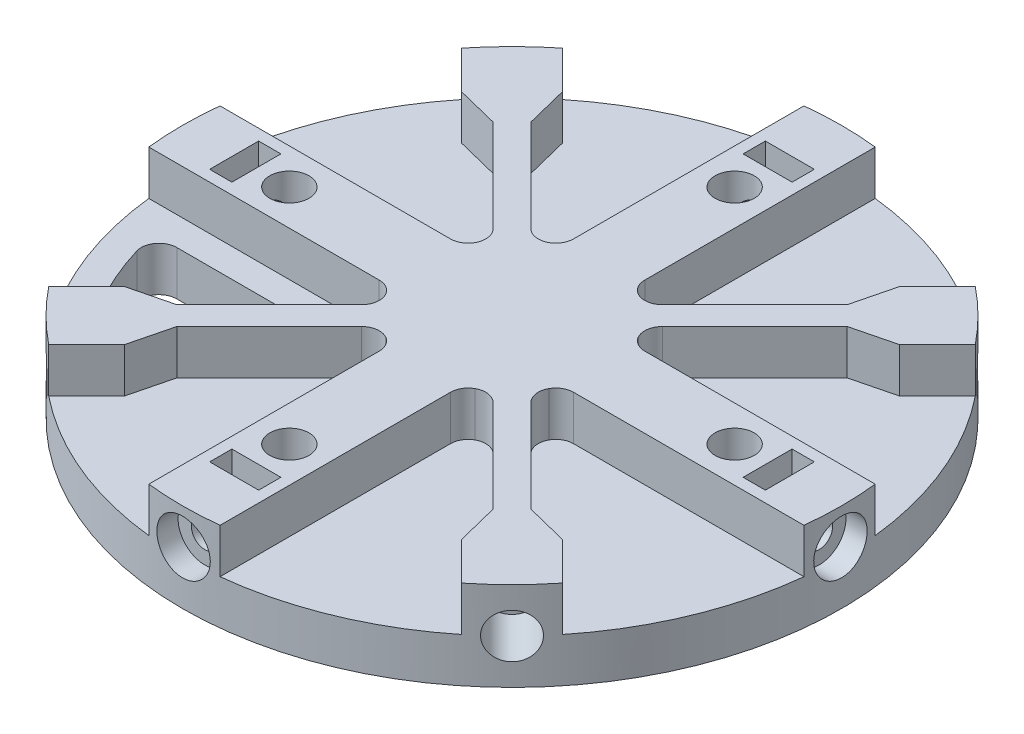
SolidWorks part; units mm, degrees
material "Custom Plastic"
ref_plane "Front Plane" through (0, 0, 0) normal (0, 0, 1) x (1, 0, 0)
ref_plane "Top Plane" through (0, 0, 0) normal (0, 1, 0) x (1, 0, 0)
ref_plane "Right Plane" through (0, 0, 0) normal (1, 0, 0) x (0, 0, -1)
sketch "Sketch1" plane through (0, 0, 0) normal (0, 1, 0) x (1, 0, 0)
  circle A0 centre (0, 0) radius 37
  dimension "D1" = 74
extrude "Boss-Extrude1" add sketch "Sketch1" along normal blind 10
sketch "Sketch5" plane through (0, 10, 0) normal (0, 1, 0) x (1, 0, 0)
  circle A0 centre (0, 0) radius 25 construction
  circle A1 centre (0, 0) radius 37 construction
  point P3 (0, 25)
  point P6 (0, 37)
  point P7 (25, 0)
  point P8 (0, -25)
  point P9 (-25, 0)
  dimension "D1" = 12
  dimension "D2" = 4
hole_wizard "Ø4.0mm Dowel Hole2" positions "Sketch6" profile "Sketch7" hole size "Ø4.0" standard "ANSI Metric"
sketch "Sketch6" plane through (0, 10, 0) normal (0, 1, 0) x (1, 0, 0)
  point P0 (0, 25)
  point P3 (25, 0)
  point P6 (0, -25)
  point P9 (-25, 0)
sketch "Sketch7" plane through (0, 10, -25) normal (1, 0, 0) x (0, 0, 1)
  line L0 (0, 0) -> (0, 9.999)
  line L1 (0, 9.999) -> (2.2, 9.999)
  line L2 (2.2, 9.999) -> (2.2, 0)
  line L5 (2.2, 0) -> (0, 0)
  line L10 (0, 9.999) -> (-2.2, 9.999) construction
  line L11 (0, -6.35) -> (0, 107.95) construction
  dimension "Hole Dia." = 4.4
  dimension "Hole Depth" = 9.999
  dimension "Drill Angle" = 180
ref_plane "Plane1" through (37, 0, 0) normal (1, 0, 0) x (0, 0, -1)
hole_wizard "CBORE for M6 Hex Head Bolt4" positions "Sketch10" profile "Sketch11" counterbore size "M6" standard "ANSI Metric"
sketch "Sketch10" plane through (37, 0, 0) normal (1, 0, 0) x (0, 0, -1)
  point P0 (0, 6)
  dimension "D1" = 6
sketch "Sketch11" plane through (37, 6, 0) normal (0, 1, 0) x (0, 0, -1)
  line L0 (0, 0) -> (0, 11)
  line L1 (0, 11) -> (1.5, 11)
  line L2 (1.5, 11) -> (1.5, 2.5)
  line L3 (1.5, 2.5) -> (3, 2.5)
  line L4 (3, 2.5) -> (3, 0)
  line L5 (3, 0) -> (0, 0)
  line L10 (0, 11) -> (-1.5, 11) construction
  line L11 (0, -6.35) -> (0, 107.95) construction
  dimension "Hole Dia." = 3
  dimension "Hole Depth" = 11
  dimension "C'Bore Dia." = 6
  dimension "C'Bore Depth" = 2.5
  dimension "Drill Angle" = 180
pattern_circular "CirPattern1" count 4 over 360 about axis through (0, 10, 0) along (0, -1, 0) of "CBORE for M6 Hex Head Bolt4"
ref_plane "Plane2" through (26.163, 0, 26.163) normal (0.7071, 0, 0.7071) x (0, -1, 0)
sketch "Sketch18" plane through (26.163, 0, 26.163) normal (0.7071, 0, 0.7071) x (0, -1, 0)
  line L0 (0, 0) -> (-10, 0) construction
  line L1 (-10, 37) -> (-10, -37) construction
  circle A0 centre (-5, 0) radius 2.5
  dimension "D1" = 5
extrude "Cut-Extrude2" cut sketch "Sketch18" against normal blind 6.5
sketch "Sketch19" plane through (0, 10, 0) normal (0, 1, 0) x (1, 0, 0)
  line L0 (-36.7831, -4) -> (-9.6569, -4)
  line L1 (-21.0599, -15.403) -> (-28.838, -23.1812)
  line L2 (-37, 0) -> (0, 0) construction
  line L3 (0, 0) -> (-26.163, -26.163) construction
  line L5 (-4, -36.7831) -> (-4, -9.6569)
  line L7 (-21.0599, -15.403) -> (-15.403, -21.0599)
  line L8 (-15.403, -21.0599) -> (-23.1812, -28.838)
  circle A0 centre (0, 0) radius 37 construction
  arc A1 (-36.7831, -4) -> (-28.838, -23.1812) centre (0, 0) ccw
  arc A2 (-4, -36.7831) -> (-23.1812, -28.838) centre (0, 0) cw
  arc A3 (-9.6569, -4) -> (-4, -9.6569) centre (0, 0) ccw
  point P15 (-18.2314, -18.2314)
  dimension "D1" = 4
  dimension "D2" = 45
  dimension "D3" = 4
  dimension "D4" = 11
extrude "Cut-Extrude3" cut sketch "Sketch19" against normal blind 5
pattern_circular "CirPattern4" count 4 over 270 about axis through (0, 10, 0) along (0, 1, 0) of "Cut-Extrude3"
pattern_circular "CirPattern2" count 4 over 360 about axis through (0, 0, 0) along (0, 1, 0) of "Cut-Extrude2"
sketch "Sketch21" plane through (0, 5, 0) normal (0, 1, 0) x (1, 0, 0)
  line L0 (-19.2921, -17.1708) -> (-8.3752, -6.2539)
  line L1 (-21.0599, -15.403) -> (-15.403, -21.0599) construction
  line L2 (-21.0599, -15.403) -> (-15.403, -21.0599) construction
  line L3 (-6.2539, -8.3752) -> (-17.1708, -19.2921)
  line L4 (-26.163, -26.163) -> (0, 0) construction
  line L5 (-19.2921, -17.1708) -> (-17.1708, -19.2921)
  line L6 (0, 0) -> (0, -37) construction
  line L7 (19.2921, -17.1708) -> (8.3752, -6.2539)
  line L8 (19.2921, -17.1708) -> (17.1708, -19.2921)
  line L9 (6.2539, -8.3752) -> (17.1708, -19.2921)
  line L10 (0, 0) -> (37, 0) construction
  line L11 (6.2539, 8.3752) -> (17.1708, 19.2921)
  line L12 (19.2921, 17.1708) -> (17.1708, 19.2921)
  line L13 (19.2921, 17.1708) -> (8.3752, 6.2539)
  line L14 (-19.2921, 17.1708) -> (-8.3752, 6.2539)
  line L15 (-19.2921, 17.1708) -> (-17.1708, 19.2921)
  line L16 (-6.2539, 8.3752) -> (-17.1708, 19.2921)
  arc A0 (-9.6569, -4) -> (-4, -9.6569) centre (0, 0) ccw construction
  arc A1 (-28.838, -23.1812) -> (-23.1812, -28.838) centre (0, 0) ccw construction
  arc A2 (-9.6569, -4) -> (-4, -9.6569) centre (0, 0) ccw construction
  arc A3 (-8.3752, -6.2539) -> (-6.2539, -8.3752) centre (0, 0) ccw
  arc A4 (-4, -36.7831) -> (4, -36.7831) centre (0, 0) ccw construction
  arc A5 (8.3752, -6.2539) -> (6.2539, -8.3752) centre (0, 0) cw
  arc A6 (36.7831, -4) -> (36.7831, 4) centre (0, 0) ccw construction
  arc A7 (8.3752, 6.2539) -> (6.2539, 8.3752) centre (0, 0) ccw
  arc A8 (-8.3752, 6.2539) -> (-6.2539, 8.3752) centre (0, 0) cw
  dimension "D1" = 1.5
  dimension "D2" = 3
extrude "Boss-Extrude5" add sketch "Sketch21" along normal up to surface (5 mm away) up to face at (-22.1589, 10, 22.1589)
chamfer "Chamfer1" distance 3 distance2 5 4 edges at (15.403, 7.5, -21.0599) (21.0599, 7.5, 15.403) (-15.403, 7.5, 21.0599) (-21.0599, 7.5, -15.403) first distance on face at (16.2869, 7.5, -20.176) first distance on face at (20.176, 7.5, 16.2869) first distance on face at (-16.2869, 7.5, 20.176) first distance on face at (-20.176, 7.5, -16.2869)
chamfer "Chamfer2" distance 5 distance2 3 4 edges at (21.0599, 7.5, -15.403) (15.403, 7.5, 21.0599) (-21.0599, 7.5, 15.403) (-15.403, 7.5, -21.0599) first distance on face at (24.949, 7.5, -19.2921) first distance on face at (19.2921, 7.5, 24.949) first distance on face at (-24.949, 7.5, 19.2921) first distance on face at (-19.2921, 7.5, -24.949)
ref_plane "Plane3" through (0, 0, 28.7) normal (0, 0, 1) x (1, 0, 0)
sketch "Sketch36" plane through (0, 0, 28.7) normal (0, 0, -1) x (-1, 0, 0)
  line L2 (-2.75, 10) -> (-2.75, 4.4123)
  line L3 (-2.75, 4.4123) -> (0, 2.8246)
  line L4 (0, 2.8246) -> (2.75, 4.4123)
  line L5 (2.75, 4.4123) -> (2.75, 10)
  line L8 (-2.75, 10) -> (2.75, 10)
  line L10 (4, 10) -> (-4, 10) construction
  line L11 (-1.375, 8.3816) -> (-2.75, 7.5877) [skipped]
  line L12 (2.75, 7.5877) -> (1.375, 8.3816) [skipped]
  circle A0 centre (0, 6) radius 2.75 construction
  dimension "D2" = 5.5
  dimension "D1" = 5.5
extrude "Cut-Extrude9" cut sketch "Sketch36" against normal blind 2.5
pattern_circular "CirPattern8" count 4 over 360 about axis through (0, 10, 0) along (0, -1, 0) of "Cut-Extrude9" reverse direction yes
fillet "Fillet15" radius 2 16 edges at (6.2539, 7.5, -8.3752) (8.3752, 7.5, -6.2539) (9.6569, 7.5, -4) (9.6569, 7.5, 4) (8.3752, 7.5, 6.2539) (6.2539, 7.5, 8.3752) (4, 7.5, 9.6569) (-8.3752, 7.5, 6.2539) (-9.6569, 7.5, 4) (-4, 7.5, 9.6569) (-6.2539, 7.5, 8.3752) (4, 7.5, -9.6569) (-4, 7.5, -9.6569) (-6.2539, 7.5, -8.3752) (-8.3752, 7.5, -6.2539) (-9.6569, 7.5, -4)
sketch "Sketch44" plane through (0, 5, 0) normal (0, 1, 0) x (1, 0, 0)
  line L5 (-21.5174, -14.8705) -> (-29.3174, -16.8206)
  line L6 (-24.5954, -18.9385) -> (-19.8814, -17.76) construction
  line L8 (-21.5174, -14.8705) -> (-13.8468, -7.2)
  line L9 (-13.8468, -7.2) -> (-33.0242, -7.2)
  line L10 (-28.4428, -18.2605) -> (-26.2314, -16.0491)
  line L11 (-26.2314, -16.0491) -> (-21.5174, -14.8705)
  line L12 (-21.5174, -14.8705) -> (-13.8468, -7.2)
  line L13 (-13.8468, -7.2) -> (-33.0242, -7.2)
  arc A6 (-33.0242, -7.2) -> (-28.4428, -18.2605) centre (0, 0) ccw
  arc A7 (-33.0242, -7.2) -> (-29.3174, -16.8206) centre (0, 0) ccw
  dimension "D1" = 3.2
extrude "Cut-Extrude12" cut sketch "Sketch44" against normal up to surface (5 mm away) up to face at (0, 0, -22.8)
fillet "Fillet16" radius 2 4 edges at (-33.0242, 2.5, 7.2) (-13.8468, 2.5, 7.2) (-29.3174, 2.5, 16.8206) (-21.5174, 2.5, 14.8705)
